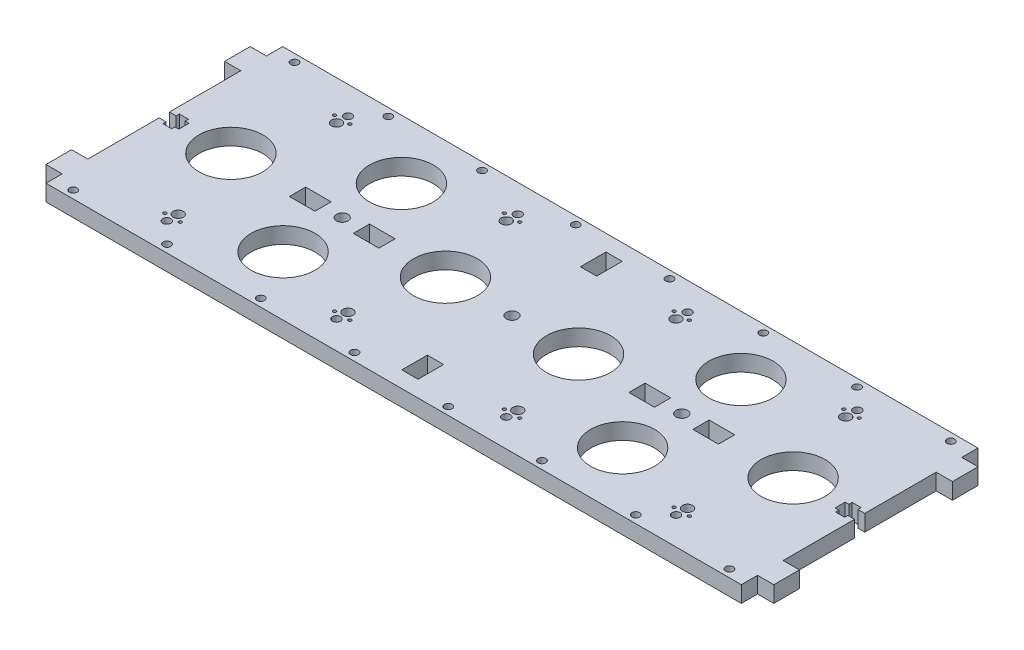
SolidWorks part; units mm, degrees
note: The reader was unsure of these and kept them because the rebuilt part matched: shared geometry of "MAIN<5>".
ref_plane "Front Plane" through (0, 0, 0) normal (0, 0, 1) x (1, 0, 0)
ref_plane "Top Plane" through (0, 0, 0) normal (0, 1, 0) x (1, 0, 0)
ref_plane "Right Plane" through (0, 0, 0) normal (1, 0, 0) x (0, 0, -1)
sketch "MAIN" plane through (0, 0, 0) normal (0, 1, 0) x (1, 0, 0)
  line L0 (-139.05, 66.35) -> (-126.35, 66.35) construction
  line L1 (-66.35, 66.35) -> (66.35, 66.35) construction
  line L2 (-66.35, 66.35) -> (-66.35, -66.35) construction
  line L3 (-66.35, -66.35) -> (66.35, -66.35) construction
  line L4 (66.35, 66.35) -> (66.35, -66.35) construction
  line L5 (-259.05, 66.35) -> (-271.75, 66.35) construction
  line L6 (-271.75, 92.5) -> (271.75, 92.5)
  line L7 (-271.75, 92.5) -> (-271.75, -92.5)
  line L8 (-271.75, -92.5) -> (271.75, -92.5)
  line L9 (271.75, 92.5) -> (271.75, -92.5)
  line L10 (0, 118.8136) -> (0, 187.9923) construction
  line L11 (-147.7, 0) -> (-117.7, 0) construction
  line L12 (-167.7, 6.35) -> (-147.7, 6.35)
  line L13 (-167.7, 6.35) -> (-167.7, -6.35)
  line L14 (-167.7, -6.35) -> (-147.7, -6.35)
  line L15 (-147.7, 6.35) -> (-147.7, -6.35)
  line L16 (-117.7, 6.35) -> (-97.7, 6.35)
  line L17 (-117.7, 6.35) -> (-117.7, -6.35)
  line L18 (-117.7, -6.35) -> (-97.7, -6.35)
  line L19 (-97.7, 6.35) -> (-97.7, -6.35)
  line L20 (147.7, 0) -> (117.7, 0) construction
  line L21 (-271.75, -79.8) -> (-284.45, -79.8)
  line L22 (-271.75, -79.8) -> (-271.75, -59.8)
  line L23 (-271.75, -59.8) -> (-284.45, -59.8)
  line L24 (-284.45, -79.8) -> (-284.45, -59.8)
  line L25 (-271.75, 79.8) -> (-284.45, 79.8)
  line L26 (-271.75, 79.8) -> (-271.75, 59.8)
  line L27 (-271.75, 59.8) -> (-284.45, 59.8)
  line L28 (-284.45, 79.8) -> (-284.45, 59.8)
  line L29 (-271.75, 4) -> (-266.45, 4)
  line L30 (-271.75, 4) -> (-271.75, -4)
  line L31 (-271.75, -4) -> (-266.45, -4)
  line L32 (-266.45, 4) -> (-266.45, -4)
  line L33 (-266.45, 6.5) -> (-259.45, 6.5)
  line L34 (-266.45, 6.5) -> (-266.45, -6.5)
  line L35 (-266.45, -6.5) -> (-259.45, -6.5)
  line L36 (-259.45, 6.5) -> (-259.45, -6.5)
  line L37 (-259.45, 4) -> (-256.45, 4)
  line L38 (-259.45, 4) -> (-259.45, -4)
  line L39 (-259.45, -4) -> (-256.45, -4)
  line L40 (-256.45, 4) -> (-256.45, -4)
  line L41 (97.7, 6.35) -> (97.7, -6.35)
  line L42 (117.7, -6.35) -> (97.7, -6.35)
  line L43 (117.7, 6.35) -> (117.7, -6.35)
  line L44 (117.7, 6.35) -> (97.7, 6.35)
  line L45 (147.7, 6.35) -> (147.7, -6.35)
  line L46 (167.7, -6.35) -> (147.7, -6.35)
  line L47 (167.7, 6.35) -> (167.7, -6.35)
  line L48 (167.7, 6.35) -> (147.7, 6.35)
  line L49 (256.45, 4) -> (256.45, -4)
  line L50 (259.45, -4) -> (256.45, -4)
  line L51 (259.45, 4) -> (259.45, -4)
  line L52 (259.45, 4) -> (256.45, 4)
  line L53 (259.45, 6.5) -> (259.45, -6.5)
  line L54 (266.45, -6.5) -> (259.45, -6.5)
  line L55 (266.45, 6.5) -> (266.45, -6.5)
  line L56 (266.45, 6.5) -> (259.45, 6.5)
  line L57 (266.45, 4) -> (266.45, -4)
  line L58 (271.75, -4) -> (266.45, -4)
  line L59 (271.75, 4) -> (271.75, -4)
  line L60 (271.75, 4) -> (266.45, 4)
  line L61 (284.45, 79.8) -> (284.45, 59.8)
  line L62 (271.75, 59.8) -> (284.45, 59.8)
  line L63 (271.75, 79.8) -> (271.75, 59.8)
  line L64 (271.75, 79.8) -> (284.45, 79.8)
  line L65 (284.45, -79.8) -> (284.45, -59.8)
  line L66 (271.75, -59.8) -> (284.45, -59.8)
  line L67 (271.75, -79.8) -> (271.75, -59.8)
  line L68 (271.75, -79.8) -> (284.45, -79.8)
  circle A0 centre (-199.05, -66.35) radius 60
  circle A1 centre (-66.35, -66.35) radius 60
  circle A2 centre (66.35, -66.35) radius 60
  circle A3 centre (199.05, -66.35) radius 60
  circle A4 centre (-66.35, 66.35) radius 60
  circle A5 centre (66.35, 66.35) radius 60
  circle A6 centre (199.05, 66.35) radius 60
  circle A7 centre (-199.05, 66.35) radius 60
  point P2 (-66.35, 0)
  point P3 (0, 66.35)
  point P25 (-271.75, 0)
  point P26 (0, 92.5)
  point P41 (-132.7, 0)
  point P42 (-132.7, 66.35)
  point P63 (-259.45, 0)
  point P64 (-266.45, 0)
  point P65 (-271.75, 0)
  dimension "D3" = 120
  dimension "D4" = 12.7
  dimension "D5" = 185
  dimension "D6" = 12.7
  dimension "D7" = 20
  dimension "D8" = 30
  dimension "D9" = 12.7
  dimension "D10" = 12.7
  dimension "D11" = 12.7
  dimension "D12" = 20
  dimension "D13" = 7
  dimension "D14" = 13
  dimension "D15" = 8
  dimension "D16" = 3
  dimension "D17" = 25
  dimension "D1" = 4
extrude "Boss-Extrude1" [suppressed] add sketch "MAIN" along normal mid plane 12.7 contours L25 L28 L27 L7 | L24 L21 L7 L23 | A7 L6 L7 L29 L34 L33 L36 L37 L40 L39 L35 L31 L8 A0 A1 A2 A3 L9 L58 L55 L54 L53 L50 L49 L52 L56 L60 A6 A5 A4 | L64 L9 L62 L61 | L9 L68 L65 L66
extrude "Boss-Extrude2" add sketch "MAIN<5>" along normal mid plane 12.7 contours L25 L28 L27 L7 | L24 L21 L7 L23 | A7 L6 L7 L29 L34 L33 L36 L37 L40 L39 L35 L31 L8 A0 A1 A2 A3 L9 L58 L55 L54 L53 L50 L49 L52 L56 L60 A6 A5 A4 | L6 A7 | L8 A0 | L8 A1 | L6 A4 | L6 A5 | L8 A2 | L8 A3 | L6 A6 | L64 L9 L62 L61 | L9 L68 L65 L66
sketch "MAIN<5>" plane through (0, 0, 0) normal (0, 1, 0) x (1, 0, 0) same geometry as "MAIN"
sketch "Sketch1" plane through (0, 0, 0) normal (0, 1, 0) x (1, 0, 0)
  line L0 (-271.75, -92.5) -> (271.75, -92.5) construction
  line L1 (-6.35, 79.8) -> (6.35, 79.8)
  line L2 (-6.35, 79.8) -> (-6.35, 59.8)
  line L3 (-6.35, 59.8) -> (6.35, 59.8)
  line L4 (6.35, 79.8) -> (6.35, 59.8)
  line L5 (-6.35, -59.8) -> (6.35, -59.8)
  line L6 (-6.35, -59.8) -> (-6.35, -79.8)
  line L7 (-6.35, -79.8) -> (6.35, -79.8)
  line L8 (6.35, -59.8) -> (6.35, -79.8)
  line L9 (0, -59.8) -> (0, 59.8) construction
  point P8 (0, -79.8)
  point P12 (0, 59.8)
  dimension "D1" = 12.7
  dimension "D2" = 20
  dimension "D3" = 12.7
extrude "Cut-Extrude1" cut sketch "Sketch1" against normal through all both and the other way through all
hole_wizard "M8 Clearance Hole1" [suppressed] positions "Sketch2" profile "Sketch3" hole size "M8" standard "ANSI Metric"
sketch "Sketch2" plane through (0, 6.35, 0) normal (0, 1, 0) x (1, 0, 0)
  line L0 (-147.7, 0) -> (-117.7, 0) construction
  line L1 (147.7, 0) -> (117.7, 0) construction
  point P0 (-132.7, 0)
  point P4 (132.7, 0)
sketch "Sketch3" plane through (-132.7, 6.35, 0) normal (1, 0, 0) x (0, 0, 1)
  line L0 (0, 0) -> (0, 12.7)
  line L1 (0, 12.7) -> (4.5, 12.7)
  line L2 (4.5, 12.7) -> (4.5, 0)
  line L5 (4.5, 0) -> (0, 0)
  line L11 (0, -6.35) -> (0, 107.95) construction
  dimension "Thru Hole Dia." = 9
  dimension "Thru Hole Depth" = 12.7
hole_wizard "M8 Clearance Hole2" positions "Sketch4" profile "Sketch5" hole size "M8" standard "ANSI Metric" end condition through all
sketch "Sketch4" plane through (0, 6.35, 0) normal (0, 1, 0) x (1, 0, 0)
  line L0 (-147.7, 0) -> (-117.7, 0) construction
  line L1 (147.7, 0) -> (117.7, 0) construction
  point P0 (-132.7, 0)
  point P4 (132.7, 0)
  point P8 (0, 0)
sketch "Sketch5" plane through (-132.7, 6.35, 0) normal (1, 0, 0) x (0, 0, 1)
  line L0 (0, 0) -> (0, 12.7)
  line L1 (0, 12.7) -> (4.5, 12.7)
  line L2 (4.5, 12.7) -> (4.5, 0)
  line L5 (4.5, 0) -> (0, 0)
  line L11 (0, -6.35) -> (0, 107.95) construction
  dimension "Thru Hole Dia." = 9
  dimension "Thru Hole Depth" = 12.7
sketch "Sketch6" plane through (0, 0, 0) normal (0, 1, 0) x (1, 0, 0)
  line L0 (-199.05, -61.85) -> (-199.05, -70.85) construction
  line L1 (-205.05, -66.35) -> (-193.05, -66.35) construction
  line L2 (-66.35, -66.35) -> (66.35, -66.35) construction
  line L3 (0, 0) -> (29.7003, 0) construction
  line L4 (-205.05, 66.35) -> (-193.05, 66.35) construction
  line L5 (-199.05, 61.85) -> (-199.05, 70.85) construction
  circle A0 centre (-199.05, -66.35) radius 12.5 construction
  circle A1 centre (-199.05, -61.85) radius 4
  circle A2 centre (-199.05, -70.85) radius 3.175
  circle A3 centre (-205.05, -66.35) radius 1.25
  circle A4 centre (-193.05, -66.35) radius 1.25
  circle A5 centre (-66.35, -66.35) radius 12.5 construction
  circle A6 centre (-66.35, -70.85) radius 3.175
  circle A7 centre (-66.35, -61.85) radius 4
  circle A8 centre (-72.35, -66.35) radius 1.25
  circle A9 centre (-60.35, -66.35) radius 1.25
  circle A10 centre (66.35, -66.35) radius 12.5 construction
  circle A11 centre (66.35, -70.85) radius 3.175
  circle A12 centre (66.35, -61.85) radius 4
  circle A13 centre (60.35, -66.35) radius 1.25
  circle A14 centre (72.35, -66.35) radius 1.25
  circle A15 centre (199.05, -66.35) radius 12.5 construction
  circle A16 centre (199.05, -70.85) radius 3.175
  circle A17 centre (199.05, -61.85) radius 4
  circle A18 centre (193.05, -66.35) radius 1.25
  circle A19 centre (205.05, -66.35) radius 1.25
  circle A20 centre (199.05, 66.35) radius 12.5 construction
  circle A21 centre (205.05, 66.35) radius 1.25
  circle A22 centre (193.05, 66.35) radius 1.25
  circle A23 centre (199.05, 61.85) radius 4
  circle A24 centre (199.05, 70.85) radius 3.175
  circle A25 centre (66.35, 66.35) radius 12.5 construction
  circle A26 centre (72.35, 66.35) radius 1.25
  circle A27 centre (60.35, 66.35) radius 1.25
  circle A28 centre (66.35, 61.85) radius 4
  circle A29 centre (66.35, 70.85) radius 3.175
  circle A30 centre (-66.35, 66.35) radius 12.5 construction
  circle A31 centre (-60.35, 66.35) radius 1.25
  circle A32 centre (-72.35, 66.35) radius 1.25
  circle A33 centre (-66.35, 61.85) radius 4
  circle A34 centre (-66.35, 70.85) radius 3.175
  circle A35 centre (-199.05, 66.35) radius 12.5 construction
  circle A36 centre (-193.05, 66.35) radius 1.25
  circle A37 centre (-205.05, 66.35) radius 1.25
  circle A38 centre (-199.05, 70.85) radius 3.175
  circle A39 centre (-199.05, 61.85) radius 4
  dimension "D1" = 25
  dimension "D3" = 8
  dimension "D4" = 6.35
  dimension "D5" = 2.5
  dimension "D2" = 9
  dimension "D6" = 12
  dimension "D7" = 4
extrude "Cut-Extrude2" cut sketch "Sketch6" against normal through all both and the other way through all
sketch "Sketch7" plane through (0, 0, 0) normal (0, 1, 0) x (1, 0, 0)
  line L0 (-132.7, -92.5) -> (-132.7, 0) construction
  line L1 (-147.7, 0) -> (-117.7, 0) construction
  line L2 (-271.75, -92.5) -> (271.75, -92.5) construction
  line L3 (132.7, 0) -> (132.7, -92.5) construction
  line L4 (147.7, 0) -> (117.7, 0) construction
  line L5 (0, 0) -> (24.6869, 0) construction
  line L6 (-271.75, 0) -> (-167.7, 0) construction
  line L7 (-97.7, 0) -> (-6.35, 0) construction
  line L8 (-271.75, -4) -> (-271.75, -59.8) construction
  line L9 (-167.7, 6.35) -> (-167.7, -6.35) construction
  line L10 (-97.7, 6.35) -> (-97.7, -6.35) construction
  line L11 (-6.35, 79.8) -> (-6.35, 59.8) construction
  line L12 (0, 0) -> (0, 60.4485) construction
  circle A0 centre (-132.7, -46.25) radius 25
  circle A1 centre (132.7, -46.25) radius 25
  circle A2 centre (132.7, 46.25) radius 25
  circle A3 centre (-132.7, 46.25) radius 25
  circle A4 centre (-219.725, 0) radius 25
  circle A5 centre (-52.025, 0) radius 25
  circle A6 centre (52.025, 0) radius 25
  circle A7 centre (219.725, 0) radius 25
  dimension "D2" = 50
  dimension "D1" = 2
extrude "Cut-Extrude3" cut sketch "Sketch7" against normal through all both and the other way through all
fillet "Fillet1" [suppressed] radius 5
hole_wizard "Ø6.0mm Dowel Hole2" positions "Sketch8" profile "Sketch9" hole size "Ø6.0" standard "ANSI Metric" end condition up to next
sketch "Sketch8" plane through (0, 6.35, 0) normal (0, 1, 0) x (1, 0, 0)
  line L0 (-256.45, 4) -> (-256.45, -4) construction
  line L1 (256.45, 4) -> (256.45, -4) construction
  line L2 (-271.75, -92.5) -> (271.75, -92.5) construction
  line L3 (0, 0) -> (28.7348, 0) construction
  point P0 (-256.45, -86.5)
  point P4 (-183.1786, -86.5)
  point P5 (-109.9071, -86.5)
  point P6 (-36.6357, -86.5)
  point P7 (36.6357, -86.5)
  point P8 (109.9071, -86.5)
  point P9 (183.1786, -86.5)
  point P10 (256.45, -86.5)
  point P30 (256.45, 86.5)
  point P31 (183.1786, 86.5)
  point P32 (109.9071, 86.5)
  point P33 (36.6357, 86.5)
  point P34 (-36.6357, 86.5)
  point P35 (-109.9071, 86.5)
  point P36 (-183.1786, 86.5)
  point P37 (-256.45, 86.5)
  dimension "D2" = 6
  dimension "D1" = 8
sketch "Sketch9" plane through (-256.45, 6.35, 86.5) normal (1, 0, 0) x (0, 0, 1)
  line L0 (0, 0) -> (0, 12.7)
  line L1 (0, 12.7) -> (3, 12.7)
  line L2 (3, 12.7) -> (3, 0)
  line L5 (3, 0) -> (0, 0)
  line L11 (0, -6.35) -> (0, 107.95) construction
  dimension "Thru Hole Dia." = 6
  dimension "Thru Hole Depth" = 12.7
equation "\"BOTTLE_DIA\"=120MM"
equation "\"HDPE_THICK\"=0.5IN"
equation "\"SUPPORT_HEIGHT\"=150MM"
equation "\"D3@MAIN\" = \"BOTTLE_DIA\""
equation "\"D4@MAIN\" = \"HDPE_THICK\""
equation "\"D6@MAIN\" = \"HDPE_THICK\""
equation "\"D9@MAIN\" = \"HDPE_THICK\""
equation "\"D10@MAIN\" = \"HDPE_THICK\""
equation "\"D11@MAIN\" = \"HDPE_THICK\""
equation "\"D1@Boss-Extrude1\"=\"HDPE_THICK\""
equation "\"D1@Boss-Extrude2\"=\"HDPE_THICK\""
equation "\"D1@Sketch1\"=\"HDPE_THICK\""
equation "\"D3@Sketch1\"=\"HDPE_THICK\""
